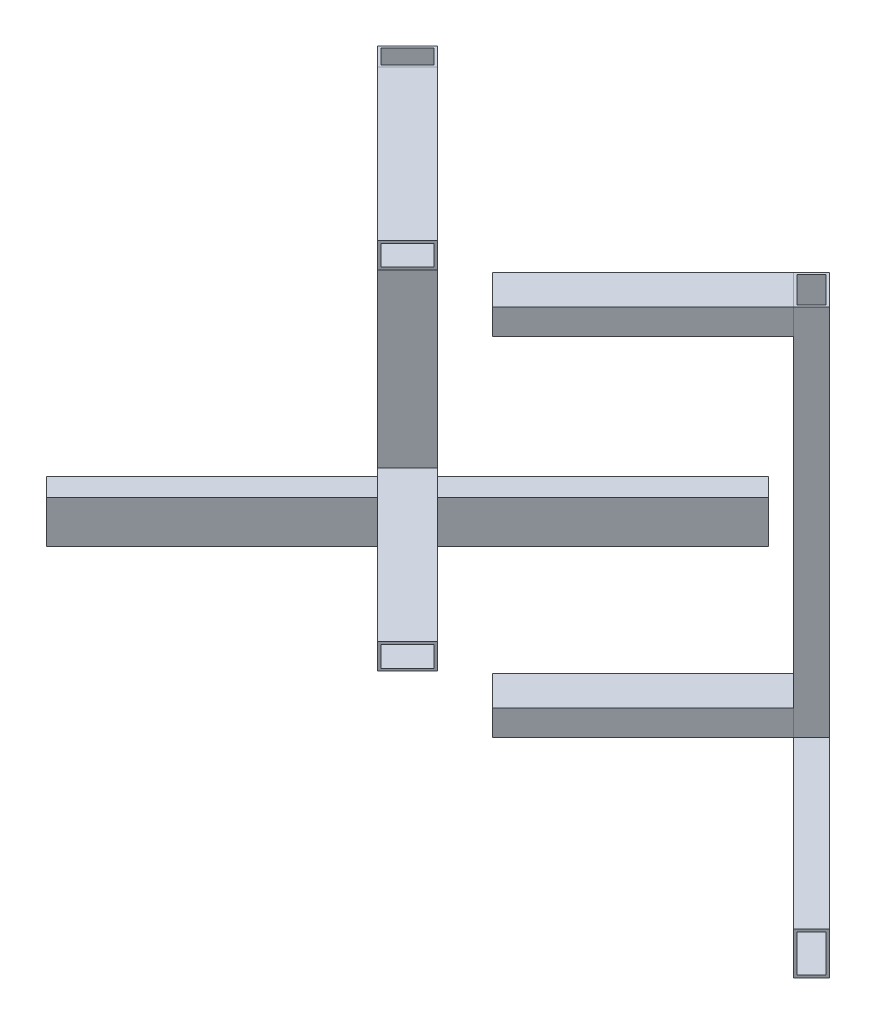
SolidWorks part; units mm, degrees
ref_plane "Front Plane" through (0, 0, 0) normal (0, 0, 1) x (1, 0, 0)
ref_plane "Top Plane" through (0, 0, 0) normal (0, 1, 0) x (1, 0, 0)
ref_plane "Right Plane" through (0, 0, 0) normal (1, 0, 0) x (0, 0, -1)
sketch "Sketch1" plane through (0, 0, 0) normal (0, 0, 1) x (1, 0, 0)
  line L1 (-300, 189.04) -> (300, 189.04)
  line L2 (-300, 189.04) -> (-300, -189.04)
  line L3 (-300, -189.04) -> (300, -189.04)
  line L4 (300, 189.04) -> (300, -189.04)
  line L5 (-300, 189.04) -> (300, -189.04) construction
  line L6 (-300, -189.04) -> (300, 189.04) construction
  point P0 (0, 0)
  dimension "D1" = 300
  dimension "D2" = 5
  dimension "D3" = 5
sketch "Sketch3" plane through (0, 0, 0) normal (1, 0, 0) x (0, 0, -1)
  line L0 (0, 189.04) -> (0, -189.04) construction
  line L1 (0, 189.04) -> (0, -189.04) construction
  line L2 (0, 0) -> (254.4636, 0) construction
  line L3 (-25, 219.04) -> (25, 219.04)
  line L4 (-25, 219.04) -> (-25, 189.04)
  line L5 (-25, 189.04) -> (25, 189.04)
  line L6 (25, 219.04) -> (25, 189.04)
  line L7 (-25, 219.04) -> (25, 189.04) construction
  line L8 (-25, 189.04) -> (25, 219.04) construction
  line L9 (-22, 216.04) -> (-22, 192.04)
  line L10 (-22, 192.04) -> (22, 192.04)
  line L11 (22, 216.04) -> (22, 192.04)
  line L12 (-22, 216.04) -> (22, 216.04)
  line L13 (-22, -216.04) -> (22, -216.04)
  line L14 (22, -216.04) -> (22, -192.04)
  line L15 (-22, -192.04) -> (22, -192.04)
  line L16 (-22, -216.04) -> (-22, -192.04)
  line L17 (-25, -189.04) -> (25, -189.04)
  line L18 (25, -219.04) -> (25, -189.04)
  line L19 (-25, -219.04) -> (25, -219.04)
  line L20 (-25, -219.04) -> (-25, -189.04)
  point P2 (0, 204.04)
  dimension "D1" = 30
  dimension "D2" = 50
  dimension "D3" = 3
extrude "Boss-Extrude2" [suppressed] add sketch "Sketch3" along normal up to vertex and the other way up to vertex separate body
sketch "Sketch2" plane through (0, 0, 0) normal (0, 1, 0) x (1, 0, 0)
  line L0 (0, 0) -> (0, 67.8962) construction
  line L1 (300, -25) -> (330, -25)
  line L2 (300, -25) -> (300, 25)
  line L3 (300, 25) -> (330, 25)
  line L4 (330, -25) -> (330, 25)
  line L5 (300, -25) -> (330, 25) construction
  line L6 (300, 25) -> (330, -25) construction
  line L7 (-300, 0) -> (300, 0) construction
  line L8 (-300, 0) -> (300, 0) construction
  line L9 (-300, 25) -> (-330, -25) construction
  line L10 (-300, -25) -> (-330, 25) construction
  line L11 (-330, -25) -> (-330, 25)
  line L12 (-300, 25) -> (-330, 25)
  line L13 (-300, -25) -> (-300, 25)
  line L14 (-300, -25) -> (-330, -25)
  line L15 (327, -22) -> (327, 22)
  line L16 (303, 22) -> (327, 22)
  line L17 (303, -22) -> (303, 22)
  line L18 (303, -22) -> (327, -22)
  line L19 (-303, 22) -> (-327, 22)
  line L20 (-327, -22) -> (-327, 22)
  line L21 (-303, -22) -> (-327, -22)
  line L22 (-303, -22) -> (-303, 22)
  point P0 (315, 0)
  point P17 (-315, 0)
  dimension "D1" = 50
  dimension "D2" = 30
  dimension "D3" = 3
extrude "Boss-Extrude1" [suppressed] add sketch "Sketch2" along normal up to vertex and the other way up to vertex separate body
sketch "Sketch5" [suppressed] plane through (0, 0, 0) normal (0, 0, 1) x (1, 0, 0)
  line L0 (300, -219.04) -> (330, -219.04) construction
  line L1 (300, -269.04) -> (330, -269.04)
  line L2 (300, -269.04) -> (300, -219.04)
  line L3 (300, -219.04) -> (330, -219.04)
  line L4 (330, -269.04) -> (330, -219.04)
  line L5 (300, -269.04) -> (330, -219.04) construction
  line L6 (300, -219.04) -> (330, -269.04) construction
  line L7 (0, 0) -> (0, -287.0389) construction
  line L8 (-300, 189.04) -> (300, -189.04) construction
  line L9 (327, -266.04) -> (327, -222.04)
  line L10 (303, -222.04) -> (327, -222.04)
  line L11 (303, -266.04) -> (303, -222.04)
  line L12 (303, -266.04) -> (327, -266.04)
  line L13 (-300, -219.04) -> (-330, -269.04) construction
  line L14 (-300, -269.04) -> (-330, -219.04) construction
  line L15 (-303, -266.04) -> (-327, -266.04)
  line L16 (-303, -266.04) -> (-303, -222.04)
  line L17 (-303, -222.04) -> (-327, -222.04)
  line L18 (-327, -266.04) -> (-327, -222.04)
  line L19 (-330, -269.04) -> (-330, -219.04)
  line L20 (-300, -219.04) -> (-330, -219.04)
  line L21 (-300, -269.04) -> (-300, -219.04)
  line L22 (-300, -269.04) -> (-330, -269.04)
  point P0 (315, -244.04)
  point P16 (-315, -244.04)
  dimension "D1" = 30
  dimension "D2" = 50
  dimension "D3" = 3
extrude "Boss-Extrude3" [suppressed] add sketch "Sketch5" along normal mid plane 600 separate body
ref_plane "Plane2" through (50, 0, 0) normal (1, 0, 0) x (0, 0, -1)
ref_axis "Axis2" through (50, -293.444, 0) along (0, 1, 0)
ref_plane "Plane3" through (25, 0, -25) normal (-0.7071, 0, 0.7071) x (0, 1, 0)
sketch "Sketch8" plane through (25, 0, -25) normal (-0.7071, 0, 0.7071) x (0, 1, 0)
  line L0 (192.04, -57.3553) -> (216.04, -57.3553)
  line L1 (216.04, -13.3553) -> (216.04, -57.3553)
  line L2 (189.04, -10.3553) -> (219.04, -10.3553)
  line L3 (189.04, -10.3553) -> (189.04, -60.3553)
  line L4 (189.04, -60.3553) -> (219.04, -60.3553)
  line L5 (219.04, -10.3553) -> (219.04, -60.3553)
  line L6 (189.04, -10.3553) -> (219.04, -60.3553) construction
  line L7 (189.04, -60.3553) -> (219.04, -10.3553) construction
  line L8 (-293.444, -35.3553) -> (243.444, -35.3553) construction
  line L9 (189.04, 212.132) -> (189.04, -212.132) construction
  line L10 (0, 0) -> (0, -113.5358) construction
  line L11 (192.04, -13.3553) -> (216.04, -13.3553)
  line L12 (192.04, -13.3553) -> (192.04, -57.3553)
  line L13 (-189.04, -60.3553) -> (-219.04, -10.3553) construction
  line L14 (-189.04, -10.3553) -> (-219.04, -60.3553) construction
  line L15 (-192.04, -13.3553) -> (-192.04, -57.3553)
  line L16 (-192.04, -13.3553) -> (-216.04, -13.3553)
  line L17 (-219.04, -10.3553) -> (-219.04, -60.3553)
  line L18 (-189.04, -60.3553) -> (-219.04, -60.3553)
  line L19 (-189.04, -10.3553) -> (-189.04, -60.3553)
  line L20 (-189.04, -10.3553) -> (-219.04, -10.3553)
  line L21 (-216.04, -13.3553) -> (-216.04, -57.3553)
  line L22 (-192.04, -57.3553) -> (-216.04, -57.3553)
  point P0 (204.04, -35.3553)
  point P20 (-204.04, -35.3553)
  dimension "D1" = 50
  dimension "D2" = 30
  dimension "D3" = 3
extrude "Boss-Extrude4" add sketch "Sketch8" against normal blind 250 separate body
sketch "Sketch9" plane through (0, 0, 0) normal (0, 1, 0) x (1, 0, 0)
  line L0 (209.099, 194.4544) -> (244.4544, 159.099) construction
  line L1 (209.099, 194.4544) -> (244.4544, 159.099) construction
  line L2 (209.099, 194.4544) -> (244.4544, 159.099)
  line L3 (209.099, 194.4544) -> (230.3122, 215.6676)
  line L4 (244.4544, 159.099) -> (265.6676, 180.3122)
  line L5 (230.3122, 215.6676) -> (265.6676, 180.3122)
  line L6 (213.3417, 194.4544) -> (230.3122, 211.4249)
  line L7 (230.3122, 211.4249) -> (261.4249, 180.3122)
  line L8 (244.4544, 163.3417) -> (261.4249, 180.3122)
  line L9 (213.3417, 194.4544) -> (244.4544, 163.3417)
  dimension "D1" = 30
  dimension "D2" = 3
extrude "Boss-Extrude5" add sketch "Sketch9" along normal up to vertex (219.04 mm away) and the other way up to vertex (219.04 mm away) separate body up to point (244.4544, 219.04, -159.099) other way up to point (244.4544, -219.04, -159.099)
ref_plane "Plane4" through (25, 0, 25) normal (0.7071, 0, 0.7071) x (0.7071, 0, -0.7071)
sketch "Sketch10" plane through (25, 0, 25) normal (0.7071, 0, 0.7071) x (0.7071, 0, -0.7071)
  line L0 (285.3553, -219.04) -> (315.3553, -219.04) construction
  line L1 (285.3553, -219.04) -> (315.3553, -219.04) construction
  line L2 (288.3553, -222.04) -> (288.3553, -266.04)
  line L3 (285.3553, -219.04) -> (315.3553, -219.04)
  line L4 (285.3553, -219.04) -> (285.3553, -269.04)
  line L5 (285.3553, -269.04) -> (315.3553, -269.04)
  line L6 (315.3553, -219.04) -> (315.3553, -269.04)
  line L7 (288.3553, -266.04) -> (312.3553, -266.04)
  line L8 (312.3553, -222.04) -> (312.3553, -266.04)
  line L9 (288.3553, -222.04) -> (312.3553, -222.04)
  dimension "D1" = 50
  dimension "D2" = 3
extrude "Boss-Extrude6" add sketch "Sketch10" along normal mid plane 600 separate body
mirror "Mirror1" about plane through (0, 0, 0) normal (1, 0, 0) of bodies 108 109 110 111
